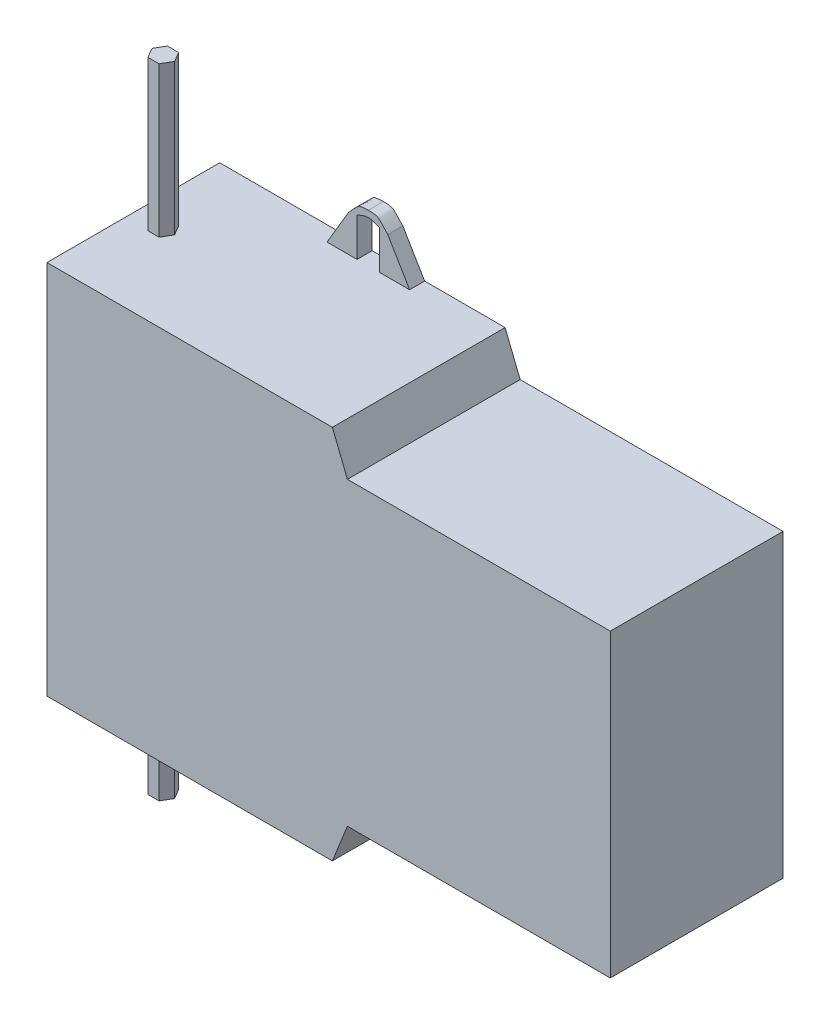
SolidWorks part; units mm, degrees
ref_plane "Front Plane" through (0, 0, 0) normal (0, 0, 1) x (1, 0, 0)
ref_plane "Top Plane" through (0, 0, 0) normal (0, 1, 0) x (1, 0, 0)
ref_plane "Right Plane" through (0, 0, 0) normal (1, 0, 0) x (0, 0, -1)
sketch "Sketch1" plane through (0, 0, 0) normal (0, 0, 1) x (1, 0, 0)
  line L0 (38, 50) -> (40, 45)
  line L1 (40, 5) -> (75, 5)
  line L2 (0, 0) -> (0, 50)
  line L3 (0, 50) -> (38, 50)
  line L4 (0, 25) -> (150, 25) construction
  line L5 (40, 45) -> (75, 45)
  line L6 (0, 0) -> (38, 0)
  line L7 (38, 0) -> (40, 5)
  line L8 (75, 45) -> (75, 5)
  point P6 (75, 25)
  point P9 (75, 25)
  dimension "D3" = 75
  dimension "D4" = 38
  dimension "D5" = 35
extrude "Boss-Extrude1" add sketch "Sketch1" along normal blind 23
sketch "Sketch2" plane through (0, 0, 0) normal (0, 0, -1) x (-1, 0, 0)
  line L0 (-27.2831, 50) -> (-24.3764, 54.9155)
  line L1 (-38, 50) -> (0, 50) construction
  line L2 (-19.1897, 54.9155) -> (-16.2831, 50)
  line L3 (-16.2831, 50) -> (-27.2831, 50)
  line L4 (-21.7831, 50) -> (-21.7831, 55.1165) construction
  line L5 (-29.9077, 56.3) -> (-21.7831, 56.3) construction
  line L6 (-20.0084, 56.3) -> (-7.8131, 56.3) construction
  line L7 (-21.7831, 59.3012) -> (-21.7831, 65.58) construction
  line L8 (-21.7831, 55.5719) -> (-21.7831, 56.4169) construction
  line L9 (-23.2831, 50) -> (-20.2831, 50)
  line L10 (-23.2831, 50) -> (-23.2831, 55.1165)
  line L12 (-20.2831, 50) -> (-20.2831, 55.1165)
  spline S0 degree 3 poles (-24.3764, 54.9155) (-23.9195, 55.4266) (-23.0838, 56.3187) (-22.7702, 56.3298) (-22.1359, 56.4399) (-21.7831, 56.4169) knots 0 0 0 0 0.318153 0.553621 0.816427 0.816427 0.816427 0.816427
  spline S1 degree 3 poles (-19.1897, 54.9155) (-19.6466, 55.4266) (-20.4823, 56.3187) (-20.796, 56.3298) (-21.4302, 56.4399) (-21.7831, 56.4169) knots 0 0 0 0 0.318153 0.553621 0.816427 0.816427 0.816427 0.816427
  spline S2 degree 3 poles (-23.2831, 55.1165) (-22.7831, 55.3442) (-21.7831, 55.7996) (-20.7831, 55.3442) (-20.2831, 55.1165) knots 0 0 0 0 0.5 1 1 1 1
  line M4 (0, 50) -> (-38, 50)
  dimension "D1" = 11
  dimension "D2" = 6.3
  dimension "D3" = 1.5
  dimension "D4" = 3
extrude "Boss-Extrude2" add sketch "Sketch2" against normal blind 2 contours L10 S2 L12 L2 S1 S0 L0 M4 region at (25.7201, 52.3929, 0)
ref_plane "Plane1" through (0, 25, 0) normal (0, 1, 0) x (-1, 0, 0)
mirror "Mirror1" about plane through (0, 25, 0) normal (0, 1, 0) of "Boss-Extrude2"
sketch "Sketch3" plane through (0, 0, 0) normal (0, -1, 0) x (1, 0, 0)
  line L0 (0, 23) -> (0, 0) construction
  line L1 (5.3022, 11.32) -> (4.5517, 12.62)
  line L2 (4.5517, 12.62) -> (3.0506, 12.62)
  line L3 (3.0506, 12.62) -> (2.3, 11.32)
  line L4 (2.3, 11.32) -> (3.0506, 10.02)
  line L5 (3.0506, 10.02) -> (4.5517, 10.02)
  line L6 (4.5517, 10.02) -> (5.3022, 11.32)
  line L7 (16.2831, 0) -> (0, 0) construction
  circle A0 centre (3.8011, 11.32) radius 1.3 construction
  dimension "D1" = 2.6
  dimension "D2" = 2.3
  dimension "D3" = 12.62
extrude "Boss-Extrude3" add sketch "Sketch3" along normal blind 15 and the other way blind 70
